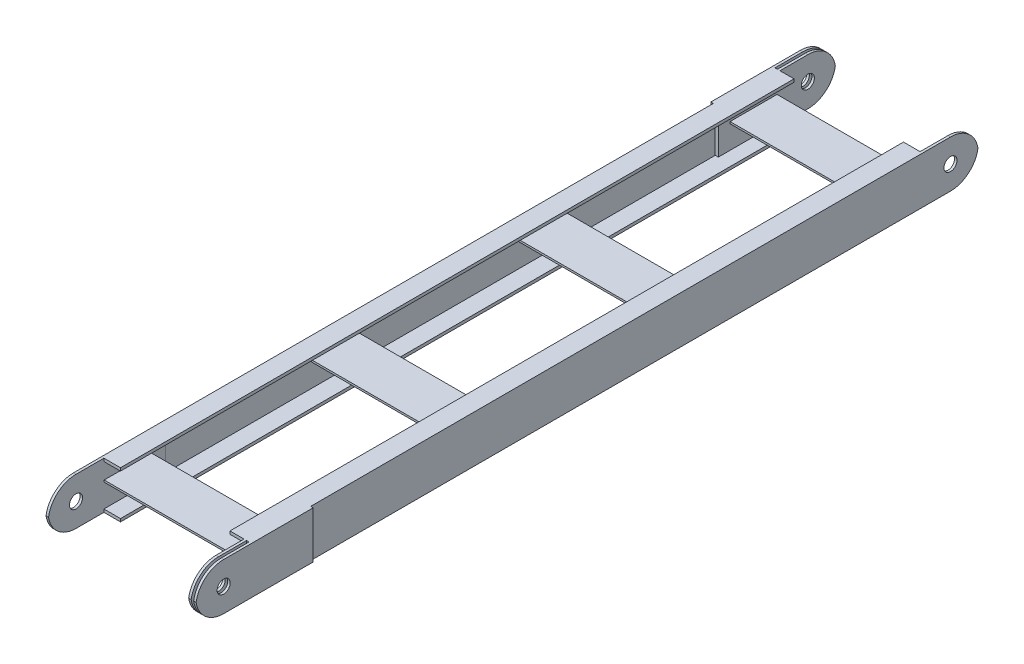
SolidWorks part; units mm, degrees
ref_plane "前视基准面" through (0, 0, 0) normal (0, 0, 1) x (1, 0, 0)
ref_plane "上视基准面" through (0, 0, 0) normal (0, 1, 0) x (1, 0, 0)
ref_plane "右视基准面" through (0, 0, 0) normal (1, 0, 0) x (0, 0, -1)
sketch "草图2" plane through (0, 0, 0) normal (0, 0, 1) x (1, 0, 0)
  line L0 (0, 0) -> (0, 160)
  line L1 (0, 160) -> (65, 160)
  line L2 (65, 160) -> (65, 150)
  line L3 (65, 150) -> (6.5, 150)
  line L4 (6.5, 150) -> (6.5, 10)
  line L5 (6.5, 10) -> (65, 10)
  line L6 (65, 10) -> (65, 0)
  line L7 (65, 0) -> (0, 0)
  line L8 (438, 160) -> (503, 160)
  line L9 (503, 160) -> (503, 0)
  line L10 (503, 0) -> (438, 0)
  line L11 (438, 0) -> (438, 10)
  line L12 (438, 10) -> (496.5, 10)
  line L13 (496.5, 10) -> (496.5, 150)
  line L14 (496.5, 150) -> (438, 150)
  line L15 (438, 150) -> (438, 160)
  dimension "D1" = 160
  dimension "D2" = 10
  dimension "D3" = 6.5
  dimension "D4" = 65
  dimension "D5" = 503
extrude "拉伸1" add sketch "草图2" along normal blind 2675
sketch "草图5" plane through (0, 0, 0) normal (-1, 0, 0) x (0, 0, 1)
  line L0 (200, 95) -> (360, 95)
  line L1 (360, 95) -> (360, 88.5)
  line L2 (283.25, 88.5) -> (360, 88.5)
  line L3 (283.25, 88.5) -> (283.25, 48.5)
  line L4 (283.25, 48.5) -> (276.75, 48.5)
  line L5 (276.75, 48.5) -> (276.75, 88.5)
  line L6 (276.75, 88.5) -> (200, 88.5)
  line L7 (200, 88.5) -> (200, 95)
  line L8 (0, 160) -> (0, 0) construction
  point P10 (0, 80)
  dimension "D1" = 160
  dimension "D2" = 6.5
  dimension "D3" = 6.5
  dimension "D4" = 40
  dimension "D5" = 200
  dimension "D6" = 15
extrude "拉伸3" add sketch "草图5" against normal blind 503
sketch "草图6" plane through (0, 160, 0) normal (0, 1, 0) x (1, 0, 0)
  line L0 (503, 0) -> (438, 0) construction
  line L1 (494.5, 0) -> (8.5, 0)
  line L2 (494.5, 0) -> (494.5, -190)
  line L3 (494.5, -190) -> (8.5, -190)
  line L4 (8.5, 0) -> (8.5, -190)
  line L5 (65, -2675) -> (0, -2675) construction
  line L6 (494.5, -2485) -> (8.5, -2485)
  line L7 (494.5, -2485) -> (494.5, -2675)
  line L8 (494.5, -2675) -> (8.5, -2675)
  line L9 (8.5, -2485) -> (8.5, -2675)
  line L10 (503, -2675) -> (503, 0) construction
  line L11 (0, -2675) -> (0, 0) construction
  dimension "D1" = 8.5
  dimension "D2" = 8.5
  dimension "D3" = 190
  dimension "D4" = 190
  dimension "D5" = 8.5
  dimension "D6" = 8.5
extrude "拉伸4" cut sketch "草图6" against normal through all
pattern_linear "阵列(线性)1" count 4 spacing 708 along (0, 0, 1) of "拉伸3"
sketch "草图7" plane through (496.5, 0, 0) normal (-1, 0, 0) x (0, 0, 1)
  line L0 (2675, 10) -> (0, 10) construction
  line L1 (0, 10) -> (400, 10)
  line L2 (0, 10) -> (0, 150)
  line L3 (0, 150) -> (400, 150)
  line L4 (400, 10) -> (400, 150)
  line L5 (2675, 150) -> (0, 150) construction
  line L6 (2675, 150) -> (2675, 10) construction
  line L7 (2675, 10) -> (2275, 10)
  line L8 (2675, 10) -> (2675, 150)
  line L9 (2675, 150) -> (2275, 150)
  line L10 (2275, 10) -> (2275, 150)
  line L11 (0, 150) -> (0, 10) construction
  dimension "D1" = 400
  dimension "D2" = 400
extrude "拉伸5" add sketch "草图7" along normal blind 2
sketch "草图15" plane through (6.5, 0, 0) normal (1, 0, 0) x (0, 0, -1)
  line L0 (-2675, 10) -> (0, 10) construction
  line L1 (-2675, 150) -> (-2275, 150)
  line L2 (-2675, 150) -> (-2675, 10)
  line L3 (-2675, 10) -> (-2275, 10)
  line L4 (-2275, 150) -> (-2275, 10)
  line L5 (-2675, 150) -> (0, 150) construction
  line L6 (0, 10) -> (0, 150) construction
  line L7 (-400, 150) -> (0, 150)
  line L8 (-400, 150) -> (-400, 10)
  line L9 (-400, 10) -> (0, 10)
  line L10 (0, 150) -> (0, 10)
  dimension "D1" = 400
  dimension "D2" = 400
extrude "拉伸8" add sketch "草图15" along normal blind 2
sketch "草图19" plane through (503, 0, 0) normal (1, 0, 0) x (0, 0, -1)
  line L0 (-2675, 0) -> (0, 0) construction
  line L1 (-2675, 160) -> (-2275, 160)
  line L2 (-2675, 160) -> (-2675, 0)
  line L3 (-2675, 0) -> (-2275, 0)
  line L5 (-2275, 160) -> (-2275, 0)
  dimension "D1" = 400
extrude "拉伸11" add sketch "草图19" along normal blind 8.5
pattern_linear "阵列(线性)2" count 2 spacing 17 along (-1, 0, 0) of "拉伸11"
sketch "草图22" plane through (0, 160, 0) normal (0, 1, 0) x (1, 0, 0)
  line L0 (511.5, -2675) -> (486, -2675) construction
  line L1 (494.5, -2485) -> (503, -2485)
  line L2 (494.5, -2485) -> (494.5, -2675)
  line L3 (494.5, -2675) -> (503, -2675)
  line L4 (503, -2485) -> (503, -2675)
  line L5 (511.5, -2275) -> (511.5, -2675) construction
  line L6 (486, -2485) -> (486, -2675) construction
  line L7 (486, -2485) -> (438, -2485) construction
  dimension "D1" = 8.5
  dimension "D2" = 8.5
extrude "拉伸12" cut sketch "草图22" against normal through all
sketch "草图23" plane through (0, 0, 0) normal (-1, 0, 0) x (0, 0, 1)
  line L0 (0, 160) -> (0, 0) construction
  line L2 (2675, 0) -> (0, 0) construction
  line L3 (2675, 160) -> (2675, 0) construction
  line L4 (2675, 160) -> (0, 160) construction
  circle A0 centre (95, 80) radius 11
  circle A1 centre (2580, 80) radius 22.25
  dimension "D3" = 22
  dimension "D4" = 44.5
  dimension "D1" = 95
  dimension "D2" = 80
  dimension "D5" = 95
  dimension "D6" = 80
extrude "拉伸13" cut sketch "草图23" against normal through all
sketch "草图26" plane through (0, 0, 0) normal (-1, 0, 0) x (0, 0, 1)
  line L0 (0, 160) -> (0, 0)
  line L1 (0, 160) -> (400, 160)
  line L2 (400, 160) -> (400, 0)
  line L4 (0, 0) -> (400, 0)
  dimension "D1" = 400
extrude "拉伸14" add sketch "草图26" along normal blind 8.5
pattern_linear "阵列(线性)3" count 2 spacing 17 along (1, 0, 0) of "拉伸14"
sketch "草图27" plane through (0, 160, 0) normal (0, 1, 0) x (1, 0, 0)
  line L0 (17, 0) -> (-8.5, 0) construction
  line L1 (0, 0) -> (8.5, 0)
  line L2 (0, 0) -> (0, -190)
  line L3 (0, -190) -> (8.5, -190)
  line L4 (8.5, 0) -> (8.5, -190)
  line L5 (-8.5, -400) -> (-8.5, 0) construction
  line L6 (17, -190) -> (17, 0) construction
  line L7 (17, -190) -> (65, -190) construction
  dimension "D1" = 8.5
  dimension "D2" = 8.5
extrude "拉伸15" cut sketch "草图27" against normal through all
sketch "草图28" plane through (-8.5, 0, 0) normal (-1, 0, 0) x (0, 0, 1)
  line L0 (0, 160) -> (0, 0) construction
  line L1 (400, 160) -> (0, 160) construction
  circle A0 centre (95, 80) radius 22.25
  dimension "D1" = 44.5
  dimension "D2" = 95
  dimension "D3" = 80
extrude "拉伸16" cut sketch "草图28" against normal through all
fillet "圆角2" radius 95 12 edges at (4.25, 160, 2675) (4.25, 0, 2675) (507.25, 0, 2675) (490.25, 0, 2675) (507.25, 160, 2675) (490.25, 160, 2675) (-4.25, 160, 0) (12.75, 160, 0) (-4.25, 0, 0) (12.75, 0, 0) (498.75, 160, 0) (498.75, 0, 0)
